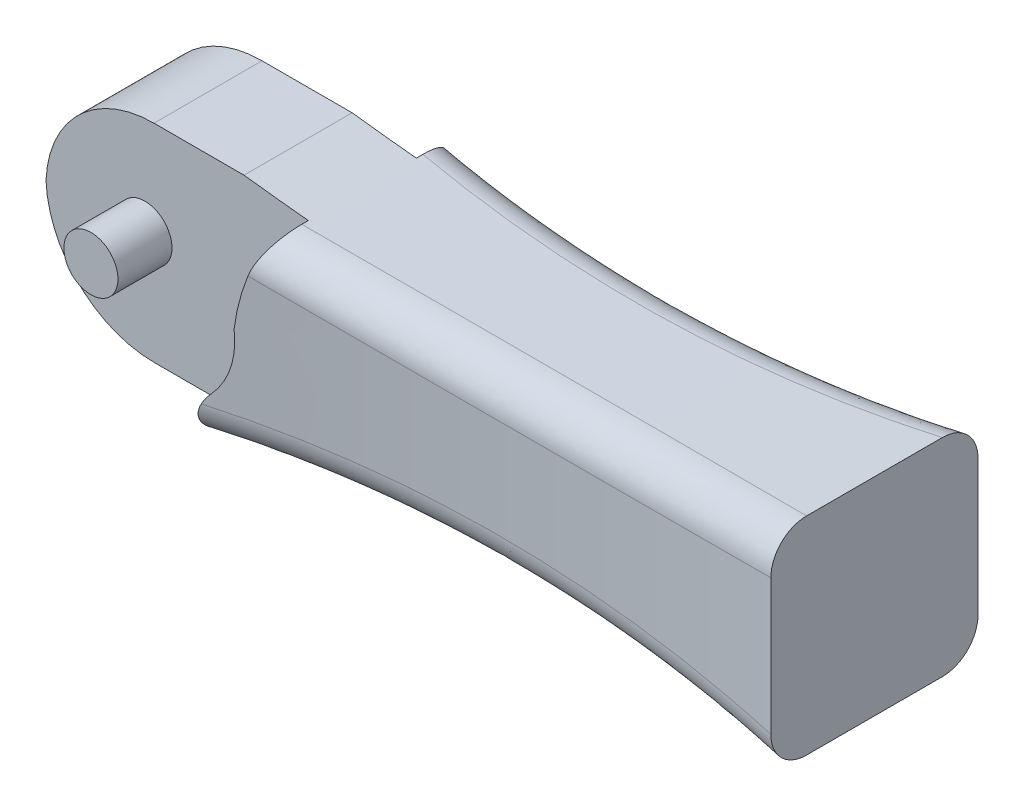
SolidWorks part; units mm, degrees
ref_plane "Front Plane" through (0, 0, 0) normal (0, 0, 1) x (1, 0, 0)
ref_plane "Top Plane" through (0, 0, 0) normal (0, 1, 0) x (1, 0, 0)
ref_plane "Right Plane" through (0, 0, 0) normal (1, 0, 0) x (0, 0, -1)
sketch "Sketch1" plane through (0, 0, 0) normal (1, 0, 0) x (0, 0, -1)
  line L1 (3, -5.75) -> (-3, -5.75)
  line L2 (3, -5.75) -> (3, 5.75)
  line L3 (3, 5.75) -> (-3, 5.75)
  line L4 (-3, -5.75) -> (-3, 5.75)
  line L5 (3, -5.75) -> (-3, 5.75) construction
  line L6 (3, 5.75) -> (-3, -5.75) construction
  point P0 (0, 0)
  dimension "D1" = 6
  dimension "D2" = 11.5
extrude "Boss-Extrude1" add sketch "Sketch1" along normal blind 11
sketch "Sketch2" plane through (0, 0, 3) normal (0, 0, 1) x (1, 0, 0)
  line L0 (11, 5.75) -> (0, 5.75) construction
  line L1 (11, 5.75) -> (11, -5.75) construction
  circle A0 centre (5.5, 0.25) radius 1.5
  dimension "D1" = 3
  dimension "D2" = 5.5
  dimension "D3" = 5.5
extrude "Boss-Extrude2" add sketch "Sketch2" along normal blind 3 and the other way blind 9
sketch "Sketch3" plane through (11, 0, 0) normal (1, 0, 0) x (0, 0, -1)
  line L1 (5.75, -5.75) -> (-5.75, -5.75)
  line L2 (5.75, -5.75) -> (5.75, 5.75)
  line L3 (5.75, 5.75) -> (-5.75, 5.75)
  line L4 (-5.75, -5.75) -> (-5.75, 5.75)
  line L5 (5.75, -5.75) -> (-5.75, 5.75) construction
  line L6 (5.75, 5.75) -> (-5.75, -5.75) construction
  point P0 (0, 0)
  dimension "D1" = 11.5
  dimension "D2" = 11.5
ref_plane "Plane1" through (43, 0, 0) normal (1, 0, 0) x (0, 0, -1)
ref_plane "Plane2" through (27, 0, 0) normal (1, 0, 0) x (0, 0, -1)
sketch "Sketch4" plane through (27, 0, 0) normal (1, 0, 0) x (0, 0, -1)
  line L1 (4.75, -4.75) -> (-4.75, -4.75)
  line L2 (4.75, -4.75) -> (4.75, 4.75)
  line L3 (4.75, 4.75) -> (-4.75, 4.75)
  line L4 (-4.75, -4.75) -> (-4.75, 4.75)
  line L5 (4.75, -4.75) -> (-4.75, 4.75) construction
  line L6 (4.75, 4.75) -> (-4.75, -4.75) construction
  point P0 (0, 0)
  dimension "D1" = 9.5
  dimension "D2" = 9.5
sketch "Sketch5" plane through (43, 0, 0) normal (1, 0, 0) x (0, 0, -1)
  line L1 (5.75, -5.75) -> (-5.75, -5.75)
  line L2 (5.75, -5.75) -> (5.75, 5.75)
  line L3 (5.75, 5.75) -> (-5.75, 5.75)
  line L4 (-5.75, -5.75) -> (-5.75, 5.75)
  line L5 (5.75, -5.75) -> (-5.75, 5.75) construction
  line L6 (5.75, 5.75) -> (-5.75, -5.75) construction
  point P8 (0, 0)
  dimension "D1" = 11.5
  dimension "D2" = 11.5
  dimension "D3" = 0
  dimension "D4" = 0
loft "Loft1" add profiles "Sketch3", "Sketch4", "Sketch5" start constraint default end constraint default connector at (11, 5.75, 5.75) connector at (27, 4.75, 4.75) connector at (43, 5.75, 5.75)
fillet "Fillet2" radius 2 4 edges
sketch "Sketch11" plane through (0, 0, -3) normal (0, 0, -1) x (-1, 0, 0)
  line L0 (-8.5, 4.5) -> (-8.5, -4.5)
  line L1 (-11, -5.75) -> (-11, 5.75) construction
  arc A0 (-8.5, 4.5) -> (-8.5, -4.5) centre (-8.5, 0) ccw
  dimension "D1" = 4.5
  dimension "D2" = 2.5
extrude "Cut-Extrude4" cut sketch "Sketch11" along normal blind 3
mirror "Mirror2" about plane through (0, 0, 0) normal (0, 0, 1) of "Cut-Extrude4"
fillet "Fillet8" radius 3 4 edges at (11, -3.7417, 4.375) (11, 3.7417, 4.375) (11, -3.7417, -4.375) (11, 3.7417, -4.375)
sketch "Sketch14" plane through (0, 0, -3) normal (0, 0, -1) x (-1, 0, 0)
  line L0 (-8.853, 6.1833) -> (-15.0956, 6.1833)
  line L2 (-8.853, 6.1833) -> (-12.9631, 0.5754)
  arc A0 (-11.8, 3.0594) -> (-11.8, -3.0594) centre (-8.5, 0) ccw construction
  spline S0 degree 2 poles (-12.9631, 0.5754) (-13.3222, 3.6081) (-15.0956, 6.1833) knots 0 0 0 1 1 1
extrude "Cut-Extrude7" cut sketch "Sketch14" along normal through all
mirror "Mirror3" about plane through (0, 0, 0) normal (0, 0, 1) of "Cut-Extrude7"
fillet "Fillet9" radius 6 2 edges at (0, 5.75, 0) (0, -5.75, 0)
